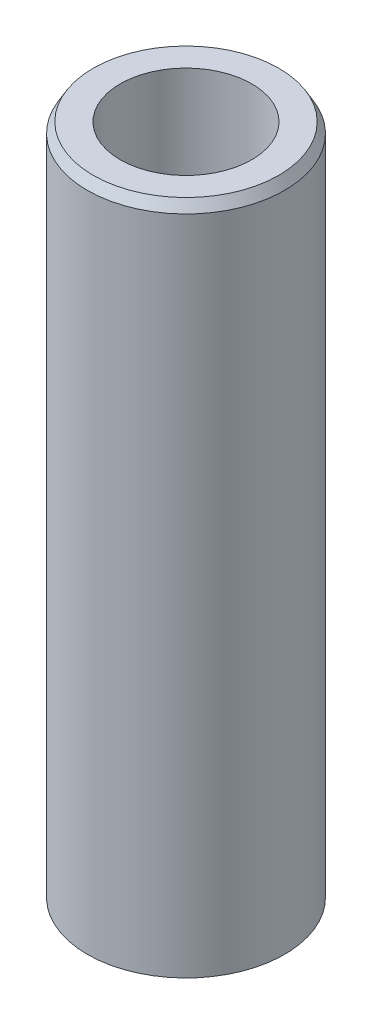
SolidWorks part; units mm, degrees
ref_plane "Front Plane" through (0, 0, 0) normal (0, 0, 1) x (1, 0, 0)
ref_plane "Top Plane" through (0, 0, 0) normal (0, 1, 0) x (1, 0, 0)
ref_plane "Right Plane" through (0, 0, 0) normal (1, 0, 0) x (0, 0, -1)
sketch "Sketch1" plane through (0, 0, 0) normal (0, 1, 0) x (1, 0, 0)
  circle A0 centre (0, 0) radius 50
  dimension "SHAFT_OD" = 100
extrude "Boss-Extrude1" add sketch "Sketch1" along normal blind 343.4836
sketch "Sketch2" plane through (0, 0, 0) normal (0, 1, 0) x (1, 0, 0)
  circle A0 centre (0, 0) radius 33.3535
  dimension "BORE_D" = 66.7071
extrude "Cut-Extrude1" cut sketch "Sketch2" along normal through all
chamfer "Chamfer1" distance 5.1325 angle 30 2 edges at (0, 343.4836, 50) (0, 0, 50) first distance on face at (0, 343.4836, 50) first distance on face at (0, 0, 33.3535)
